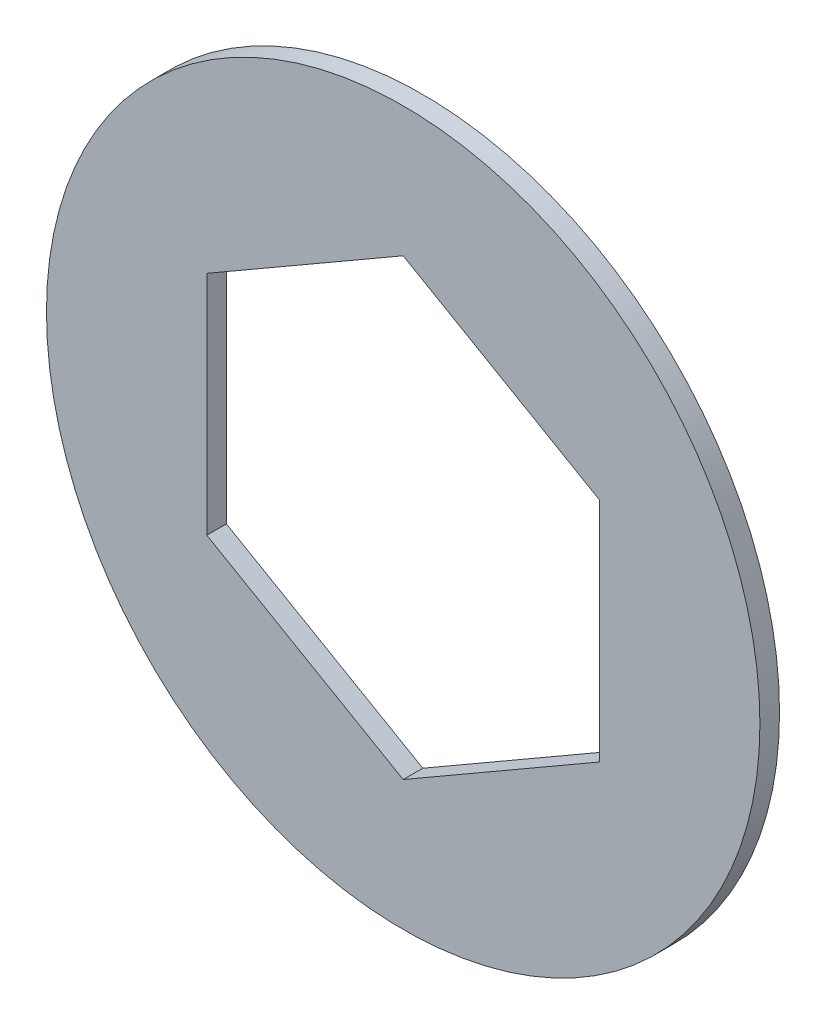
SolidWorks part; units mm, degrees
ref_plane "Plan de face" through (0, 0, 0) normal (0, 0, 1) x (1, 0, 0)
ref_plane "Plan de dessus" through (0, 0, 0) normal (0, 1, 0) x (1, 0, 0)
ref_plane "Plan de droite" through (0, 0, 0) normal (1, 0, 0) x (0, 0, -1)
sketch "Esquisse1" plane through (0, 0, 0) normal (0, 0, 1) x (1, 0, 0)
  line L1 (0, 28.9252) -> (-25.05, 14.4626)
  line L2 (-25.05, 14.4626) -> (-25.05, -14.4626)
  line L3 (-25.05, -14.4626) -> (0, -28.9252)
  line L4 (0, -28.9252) -> (25.05, -14.4626)
  line L5 (25.05, -14.4626) -> (25.05, 14.4626)
  line L6 (25.05, 14.4626) -> (0, 28.9252)
  circle A0 centre (0, 0) radius 45.5
  circle A1 centre (0, 0) radius 25.05 construction
  dimension "D1" = 91
  dimension "36" = 50.1
extrude "Boss.-Extru.1" add sketch "Esquisse1" along normal blind 2.5
ref_axis "Axis1" through (0, 0, 6.3) along (0, 0, -1)
